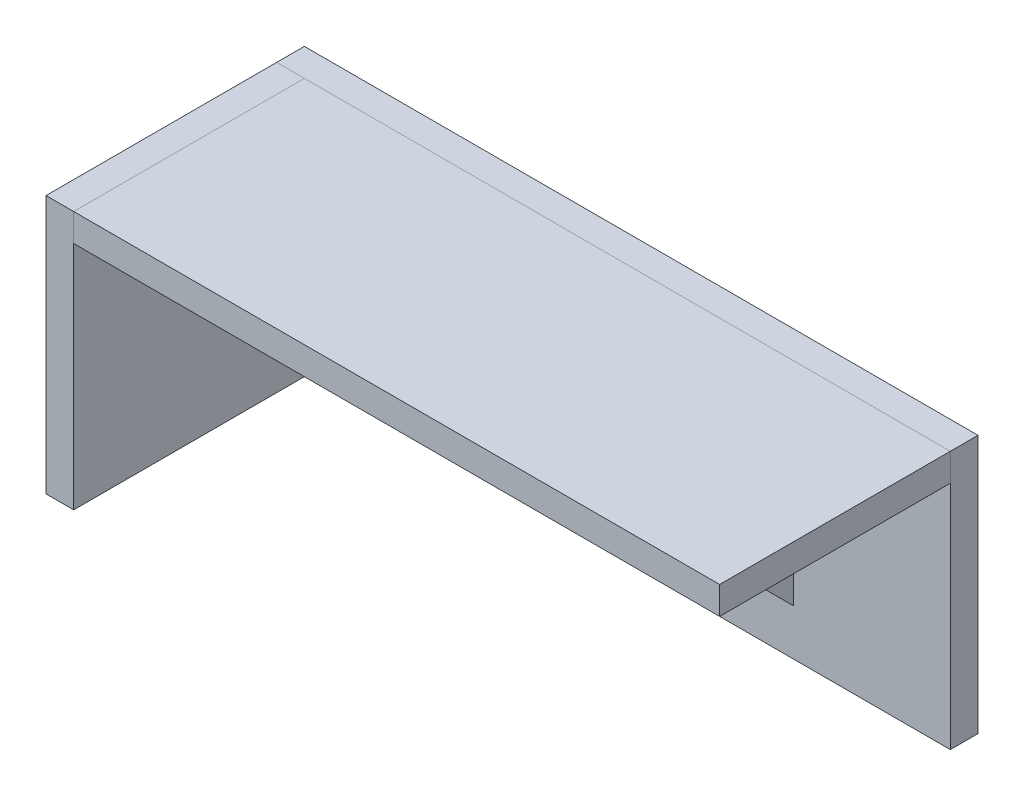
SolidWorks part; units mm, degrees
ref_plane "Front Plane" through (0, 0, 0) normal (0, 0, 1) x (1, 0, 0)
ref_plane "Top Plane" through (0, 0, 0) normal (0, 1, 0) x (1, 0, 0)
ref_plane "Right Plane" through (0, 0, 0) normal (1, 0, 0) x (0, 0, -1)
sketch "Sketch1" plane through (0, 0, 0) normal (0, 0, 1) x (1, 0, 0)
  line L1 (-56.5, 16.5) -> (16.5, 16.5)
  line L2 (-56.5, 16.5) -> (-56.5, -11.5)
  line L3 (-56.5, -11.5) -> (16.5, -11.5)
  line L4 (16.5, 16.5) -> (16.5, -11.5)
  dimension "D1" = 73
  dimension "D2" = 28
  dimension "D3" = 16.5
  dimension "D4" = 16.5
extrude "Boss-Extrude1" add sketch "Sketch1" against normal blind 3
sketch "Sketch3" plane through (0, 16.5, 0) normal (0, 1, 0) x (1, 0, 0)
  line L1 (-53.5, 0) -> (16.5, 0)
  line L2 (-53.5, 0) -> (-53.5, -25)
  line L3 (-53.5, -25) -> (16.5, -25)
  line L4 (16.5, 0) -> (16.5, -25)
  dimension "D1" = 70
  dimension "D2" = 25
extrude "Boss-Extrude2" add sketch "Sketch3" against normal blind 3 separate body
sketch "Sketch4" plane through (-53.5, 0, 0) normal (-1, 0, 0) x (0, 0, 1)
  line L1 (0, 16.5) -> (25, 16.5)
  line L2 (0, 16.5) -> (0, -11.5)
  line L3 (0, -11.5) -> (25, -11.5)
  line L4 (25, 16.5) -> (25, -11.5)
  dimension "D1" = 25
  dimension "D2" = 28
extrude "Boss-Extrude3" add sketch "Sketch4" against normal blind 3 from surface separate body starting at face at (-56.5, 2.5, -1.5)
sketch "Sketch5" plane through (-53.5, 0, 0) normal (1, 0, 0) x (0, 0, -1)
  line L0 (-20, 13.5) -> (0, -6.5)
  line L1 (-25, 13.5) -> (0, 13.5) construction
  line L2 (0, -11.5) -> (0, 16.5) construction
  line L3 (0, -6.5) -> (0, 13.5)
  line L4 (0, 13.5) -> (-20, 13.5)
  dimension "D1" = 20
  dimension "D2" = 20
extrude "Boss-Extrude4" add sketch "Sketch5" along normal blind 3 from offset 20 separate body
extrude "Boss-Extrude5" add sketch "Sketch5<2>" along normal blind 3 from offset 50 separate body
sketch "Sketch5<2>" plane through (-53.5, 0, 0) normal (1, 0, 0) x (0, 0, -1) same geometry as "Sketch5"
